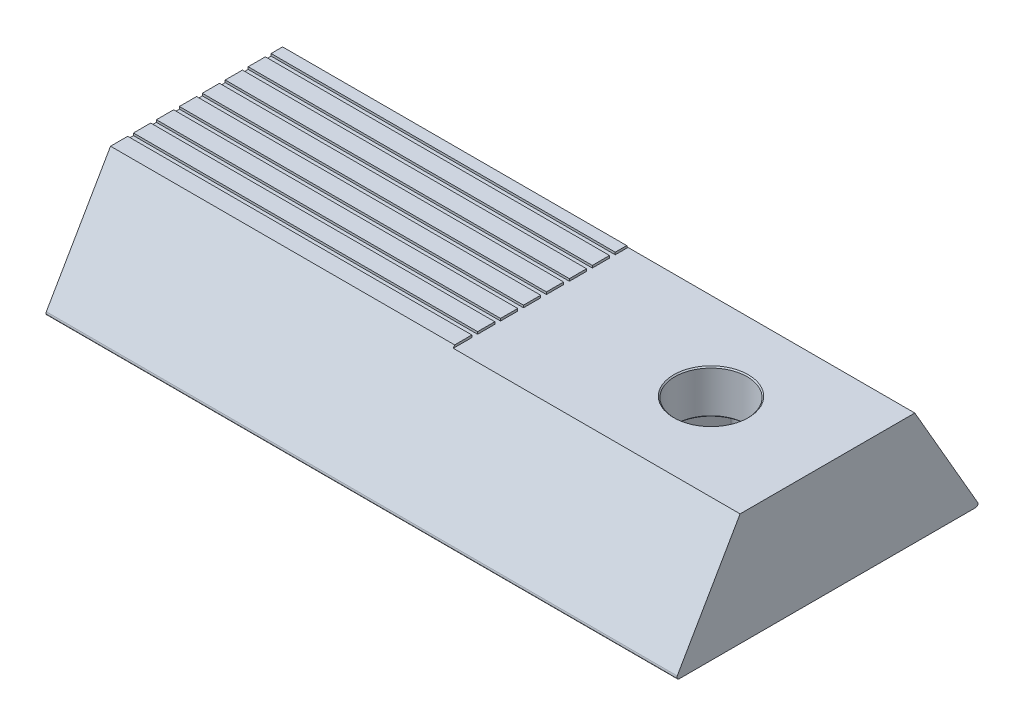
SolidWorks part; units mm, degrees
material "Copper"
ref_plane "Front Plane" through (0, 0, 0) normal (0, 0, 1) x (1, 0, 0)
ref_plane "Top Plane" through (0, 0, 0) normal (0, 1, 0) x (1, 0, 0)
ref_plane "Right Plane" through (0, 0, 0) normal (1, 0, 0) x (0, 0, -1)
sketch "Sketch1" plane through (0, 0, 0) normal (0, 1, 0) x (1, 0, 0)
  line L0 (15, 0) -> (0, 0) construction
  line L1 (-15, -7.5) -> (15, -7.5)
  line L2 (-15, -7.5) -> (-15, 7.5)
  line L3 (-15, 7.5) -> (15, 7.5)
  line L5 (0, 0) -> (0, -7.5) construction
  line L6 (15, -7.5) -> (15, 7.5) construction
  line L7 (15, -7.5) -> (40, -7.5)
  line L9 (15, 7.5) -> (40, 7.5)
  line L10 (40, -7.5) -> (40, 7.5)
  line L11 (0, 0) -> (-9, 0) construction
  line L12 (29.85, 0) -> (15, 0) construction
  circle A0 centre (29.85, 0) radius 3.15
  circle A1 centre (9, 0) radius 1.025 construction
  circle A2 centre (0, 0) radius 1.025 construction
  circle A3 centre (-9, 0) radius 1.025 construction
  dimension "D4" = 2.05
  dimension "D5" = 9
  dimension "D6" = 9
  dimension "D7" = 6.3
  dimension "D1" = 15
  dimension "D2" = 30
  dimension "D3" = 25
  dimension "D8" = 7
extrude "Boss-Extrude1" add sketch "Sketch1" along normal blind 10
sketch "Sketch2" plane through (0, 0, 0) normal (1, 0, 0) x (0, 0, -1)
  line L1 (-6, 10) -> (-5.5, 10)
  line L2 (-6, 10) -> (-6, 9.8)
  line L3 (-6, 9.8) -> (-5.5, 9.8)
  line L4 (-5.5, 10) -> (-5.5, 9.8)
  line L6 (-3.5, 10) -> (-3.5, 9.8)
  line L7 (-4, 10) -> (-3.5, 10)
  line L8 (-4, 10) -> (-4, 9.8)
  line L9 (-4, 9.8) -> (-3.5, 9.8)
  line L10 (-1.5, 10) -> (-1.5, 9.8)
  line L11 (-2, 10) -> (-1.5, 10)
  line L12 (-2, 10) -> (-2, 9.8)
  line L13 (-2, 9.8) -> (-1.5, 9.8)
  line L14 (0.5, 10) -> (0.5, 9.8)
  line L15 (0, 10) -> (0.5, 10)
  line L16 (0, 10) -> (0, 9.8)
  line L17 (0, 9.8) -> (0.5, 9.8)
  line L18 (2.5, 10) -> (2.5, 9.8)
  line L19 (2, 10) -> (2.5, 10)
  line L20 (2, 10) -> (2, 9.8)
  line L21 (2, 9.8) -> (2.5, 9.8)
  line L22 (4.5, 10) -> (4.5, 9.8)
  line L23 (4, 10) -> (4.5, 10)
  line L24 (4, 10) -> (4, 9.8)
  line L25 (4, 9.8) -> (4.5, 9.8)
  line L26 (6.5, 10) -> (6.5, 9.8)
  line L27 (6, 10) -> (6.5, 10)
  line L28 (6, 10) -> (6, 9.8)
  line L29 (6, 9.8) -> (6.5, 9.8)
  line L30 (-7.5, 10) -> (-7.5, 0) construction
  line L31 (7.5, 10) -> (-7.5, 10) construction
  dimension "D1" = 1.5
  dimension "D2" = 0.5
  dimension "D3" = 0.2
  dimension "D5" = 1.5
  dimension "D4" = 7
extrude "Cut-Extrude2" cut sketch "Sketch2" against normal through all both and the other way through all
sketch "Sketch3" plane through (0, 0, 0) normal (1, 0, 0) x (0, 0, -1)
  line L0 (7.5, 10) -> (13.0978, 0.3043)
  line L1 (12.9221, 0) -> (7.5, 0)
  line L3 (7.5, 0) -> (7.5, 10)
  line L4 (0, 0) -> (0, 14.3053) construction
  line L6 (-7.5, 0) -> (-7.5, 10)
  line L7 (-7.5, 10) -> (-13.0978, 0.3043)
  line L8 (-12.9221, 0) -> (-7.5, 0)
  line L9 (7.5, 10) -> (6.5, 10) construction
  line L10 (7.5, 10) -> (7.5, 0) construction
  arc A0 (12.9221, 0) -> (13.0978, 0.3043) centre (12.9221, 0.2029) ccw
  arc A1 (-12.9221, 0) -> (-13.0978, 0.3043) centre (-12.9221, 0.2029) cw
  point P6 (13.2735, 0)
  point P10 (-13.2735, 0)
  dimension "D2" = 26.25
  dimension "D3" = 0.2029
  dimension "D1" = 30
extrude "Boss-Extrude2" add sketch "Sketch3" along normal up to surface and the other way up to surface up to face at (40, 9.2875, -0.2187) other way up to face at (-15, 9.2875, -0.2187)
sketch "Sketch10" plane through (40, 0, 0) normal (1, 0, 0) x (0, 0, -1)
  line L0 (7.5, 10) -> (13.0978, 0.3043) construction
  line L5 (7.6155, 9.8) -> (-7.6155, 9.8)
  line L6 (7.6155, 9.8) -> (7.6155, 10)
  line L7 (7.6155, 10) -> (-7.6155, 10)
  line L8 (-7.6155, 9.8) -> (-7.6155, 10)
  line L9 (-7.5, 10) -> (-6, 10) construction
  line L10 (-6, 9.8) -> (-5.5, 9.8) construction
  line L11 (-13.0978, 0.3043) -> (-7.5, 10) construction
extrude "Cut-Extrude6" cut sketch "Sketch10" against normal blind 25
sketch "Sketch8" plane through (0, 0, 0) normal (0, -1, 0) x (1, 0, 0)
  line L3 (26.9055, -5.1) -> (32.7945, -5.1)
  line L5 (32.7945, -5.1) -> (35.739, 0)
  line L12 (35.739, 0) -> (32.7945, 5.1)
  line L13 (32.7945, 5.1) -> (26.9055, 5.1)
  line L14 (26.9055, 5.1) -> (23.961, 0)
  line L15 (23.961, 0) -> (26.9055, -5.1)
  circle A2 centre (29.85, 0) radius 3.15 construction
  circle A4 centre (29.85, 0) radius 5.1 construction
  dimension "D1" = 10.2
extrude "Cut-Extrude5" cut sketch "Sketch8" against normal blind 6
fillet "Fillet3" radius 0.5 6 edges at (32.7945, 3, -5.1) (26.9055, 3, -5.1) (23.961, 3, 0) (26.9055, 3, 5.1) (32.7945, 3, 5.1) (35.739, 3, 0)
chamfer "Chamfer1" distance 0.1 angle 45 2 edges at (29.85, 6, -3.15) (29.85, 9.8, -3.15)
